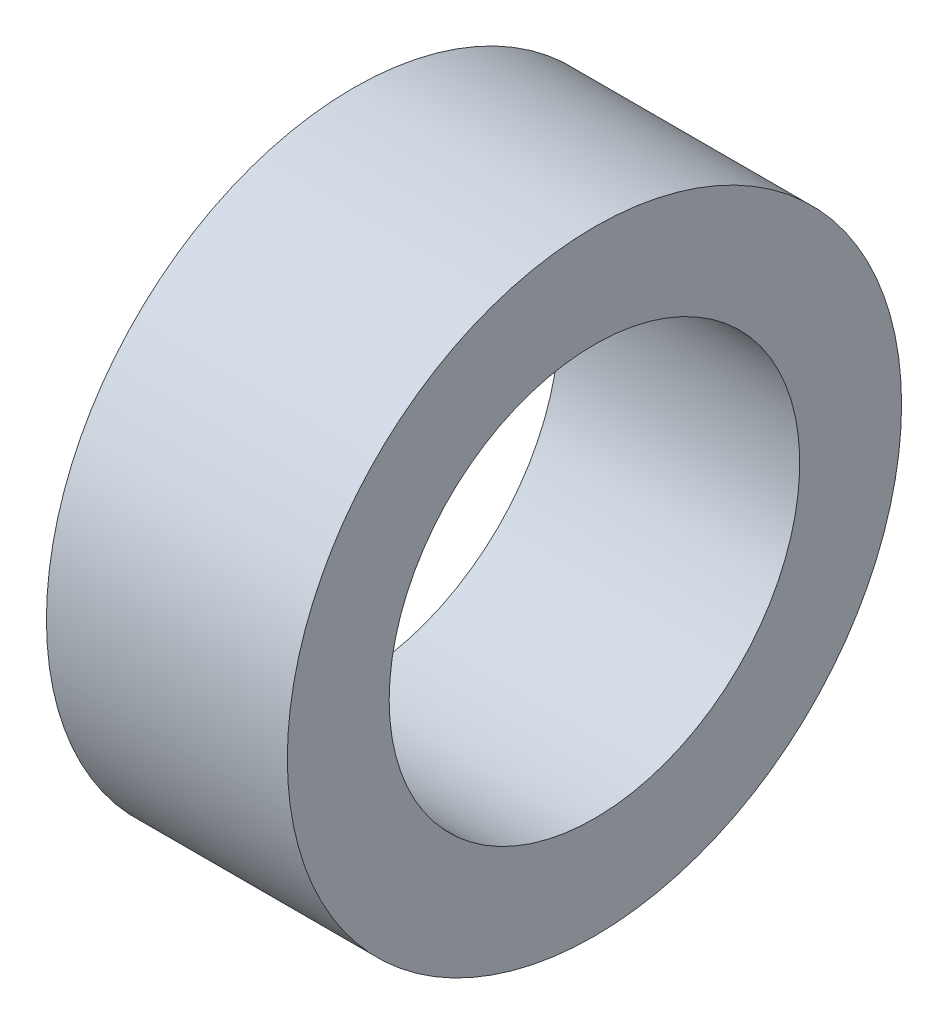
SolidWorks part; units mm, degrees
material "6061-T6 (SS)"
ref_plane "Front Plane" through (0, 0, 0) normal (0, 0, 1) x (1, 0, 0)
ref_plane "Top Plane" through (0, 0, 0) normal (0, 1, 0) x (1, 0, 0)
ref_plane "Right Plane" through (0, 0, 0) normal (1, 0, 0) x (0, 0, -1)
sketch "Sketch1" plane through (0, 0, 0) normal (0, 0, 1) x (1, 0, 0)
  line L1 (30.5156, 6.1277) -> (35.3219, 6.1277)
  line L2 (30.5156, 6.1277) -> (30.5156, 4.0957)
  line L3 (30.5156, 4.0957) -> (35.3219, 4.0957)
  line L4 (35.3219, 6.1277) -> (35.3219, 4.0957)
  line L5 (0, 0) -> (42.6651, 0) construction
  line L6 (30.5156, -12.3825) -> (30.5156, 12.3825) construction
  line L8 (35.3219, 44.9952) -> (35.3219, 10.9492) construction
  dimension "D1" = 8.1915
  dimension "D2" = 2.032
revolve "Revolve1" add sketch "Sketch1" angle 360 about L5
equation "\"D1@Sketch1\"=5/16+0.01"
